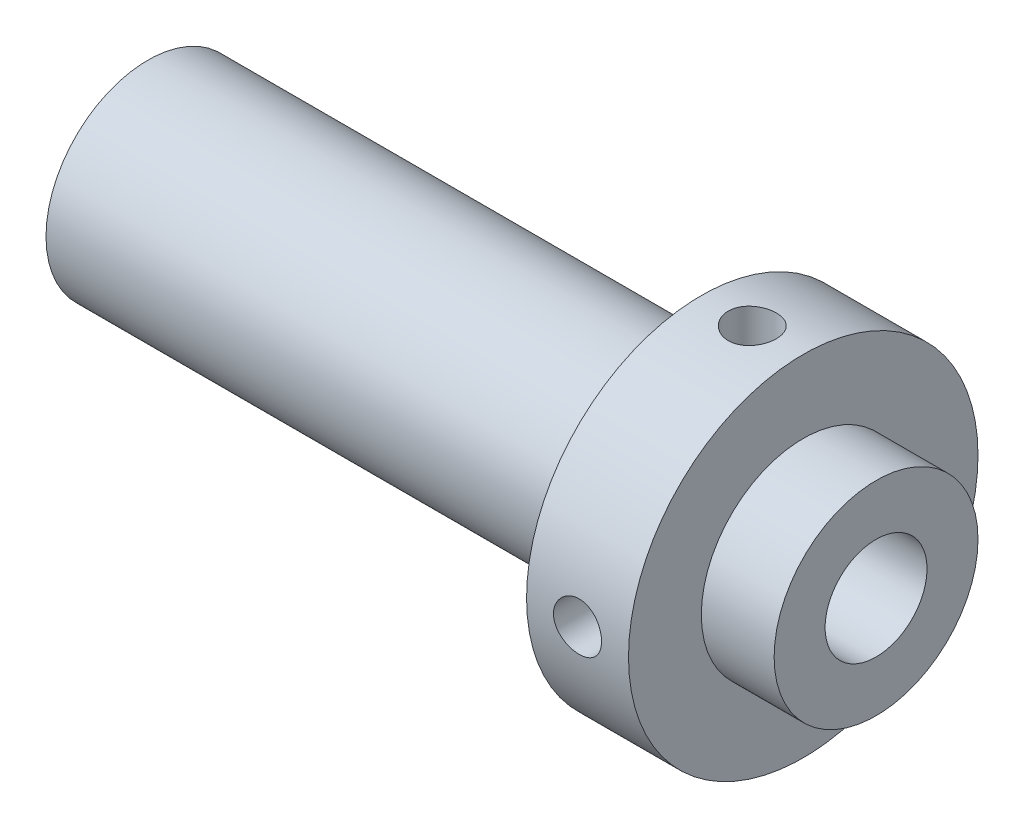
SolidWorks part; units mm, degrees
ref_plane "Front Plane" through (0, 0, 0) normal (0, 0, 1) x (1, 0, 0)
ref_plane "Top Plane" through (0, 0, 0) normal (0, 1, 0) x (1, 0, 0)
ref_plane "Right Plane" through (0, 0, 0) normal (1, 0, 0) x (0, 0, -1)
sketch "Sketch1" plane through (0, 0, 0) normal (0, 0, 1) x (1, 0, 0)
  line L0 (-5, 12) -> (-5, 7)
  line L1 (-5, 12) -> (-12, 12)
  line L2 (-12, 12) -> (-12, 7)
  line L3 (-12, 7) -> (-50, 7)
  line L4 (-50, 7) -> (-50, 0)
  line L5 (-78.3439, 0) -> (16.242, 0) construction
  line L6 (-5, 7) -> (0, 7)
  line L7 (0, 7) -> (0, 0)
  line L8 (-50, 0) -> (0, 0)
  dimension "D1" = 7
  dimension "D2" = 7
  dimension "D3" = 5
  dimension "D4" = 5
  dimension "D5" = 7
  dimension "D6" = 50
  dimension "D8" = 7
revolve "Revolve1" add sketch "Sketch1" angle 360 about L5
sketch "Sketch2" plane through (0, 0, 0) normal (1, 0, 0) x (0, 0, -1)
  circle A0 centre (0, 0) radius 3.5
  dimension "D1" = 7
ref_axis "Axis1" through (-5, 0, 0) along (-1, 0, 0)
ref_plane "Plane1" through (0, 12, 0) normal (0, 1, 0) x (1, 0, 0)
ref_plane "Plane2" through (0, 0, 12) normal (0, 0, 1) x (1, 0, 0)
hole_wizard "Trou taraudé M8x1.01" positions "Esquisse1" profile "Esquisse3" tap size "M8x1.0" standard "ISO"
sketch "Esquisse1" plane through (0, 0, 0) normal (1, 0, 0) x (0, 0, -1)
  point P0 (0, 0)
sketch "Esquisse3" plane through (0, 0, 0) normal (0, 1, 0) x (0, 0, -1)
  line L0 (0, 0) -> (0, 32.103)
  line L1 (0, 32.103) -> (3.5, 30)
  line L2 (3.5, 30) -> (3.5, 0)
  line L5 (3.5, 0) -> (0, 0)
  line L10 (0, 32.103) -> (-3.5, 30) construction
  line L11 (0, -6.35) -> (0, 107.95) construction
  dimension "Diamètre du trou pour taraudage" = 7
  dimension "Profondeur du trou pour taraudage" = 30
  dimension "Angle de pointe" = 118
cosmetic thread "Filetage de perçage1" parameters "D1"=25, "D2"=8
hole_wizard "Trou taraudé M41" positions "Esquisse4" profile "Esquisse5" tap size "M4" standard "ISO" end condition up to next
sketch "Esquisse4" plane through (0, 0, 12) normal (0, 0, 1) x (1, 0, 0)
  line L0 (-5, 0) -> (-12, 0) construction
  line L1 (-5, -12) -> (-5, 12) construction
  point P0 (-8.5, 0)
  dimension "D1" = 3.5
sketch "Esquisse5" plane through (-8.5, 0, 12) normal (1, 0, 0) x (0, -1, 0)
  line L0 (0, 0) -> (0, 8.5)
  line L1 (0, 8.5) -> (1.65, 8.5)
  line L2 (1.65, 8.5) -> (1.65, 0)
  line L5 (1.65, 0) -> (0, 0)
  line L11 (0, -6.35) -> (0, 107.95) construction
  dimension "Diamètre du trou pour taraudage jusqu'au prochain" = 3.3
  dimension "Profondeur du trou pour taraudage jusqu'au prochain" = 8.5
cosmetic thread "Filetage de perçage2" parameters "D2"=4
hole_wizard "Trou taraudé M42" positions "Esquisse6" profile "Esquisse7" tap size "M4" standard "ISO" end condition up to next
sketch "Esquisse6" plane through (0, 12, 0) normal (0, 1, 0) x (1, 0, 0)
  line L0 (-5, 0) -> (-12, 0) construction
  line L1 (-5, -7) -> (-5, 7) construction
  point P0 (-8.5, 0)
  dimension "D1" = 3.5
sketch "Esquisse7" plane through (-8.5, 12, 0) normal (1, 0, 0) x (0, 0, 1)
  line L0 (0, 0) -> (0, 8.5)
  line L1 (0, 8.5) -> (1.65, 8.5)
  line L2 (1.65, 8.5) -> (1.65, 0)
  line L5 (1.65, 0) -> (0, 0)
  line L11 (0, -6.35) -> (0, 107.95) construction
  dimension "Diamètre du trou pour taraudage jusqu'au prochain" = 3.3
  dimension "Profondeur du trou pour taraudage jusqu'au prochain" = 8.5
cosmetic thread "Filetage de perçage3" parameters "D2"=4
